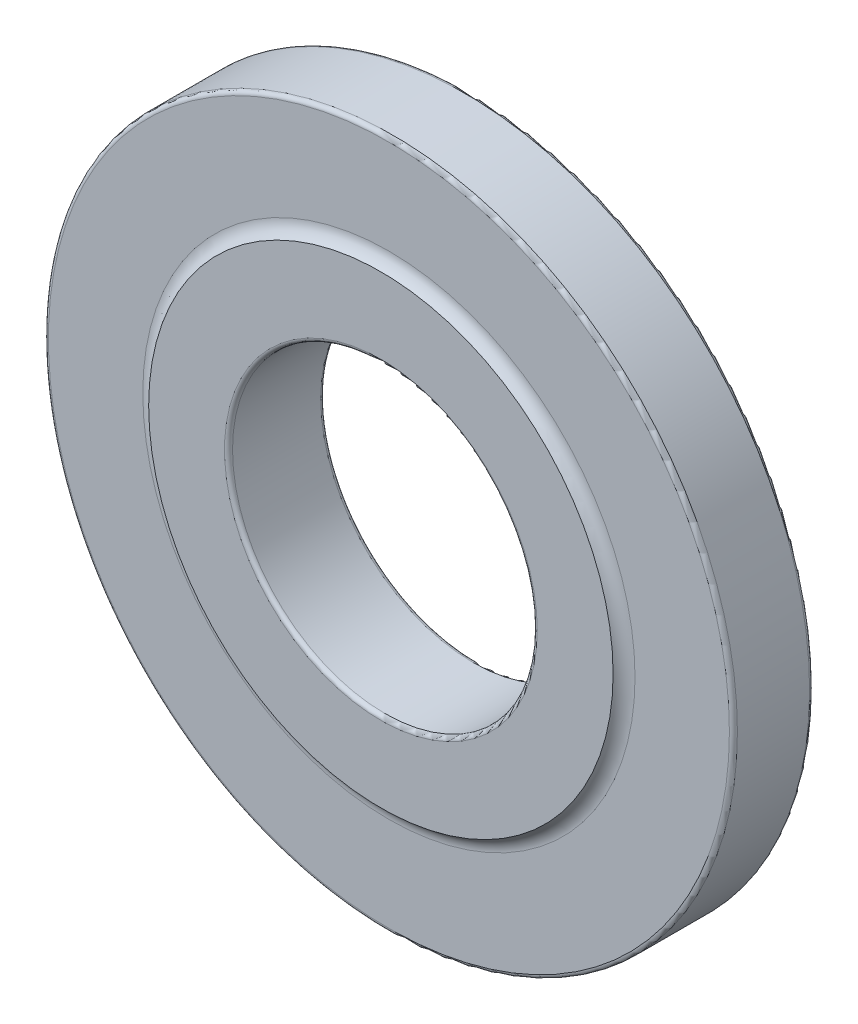
SolidWorks part; units mm, degrees
ref_plane "Plan de face" through (0, 0, 0) normal (0, 0, 1) x (1, 0, 0)
ref_plane "Plan de dessus" through (0, 0, 0) normal (0, 1, 0) x (1, 0, 0)
ref_plane "Plan de droite" through (0, 0, 0) normal (1, 0, 0) x (0, 0, -1)
sketch "Esquisse1" plane through (0, 0, 0) normal (0, 0, 1) x (1, 0, 0)
  line L0 (9.5, 0) -> (14.4778, 0) construction
  line L1 (14.4778, 0) -> (21.4762, 0) construction
  circle A0 centre (0, 0) radius 9.5
  circle A3 centre (0, 0) radius 14.4778
extrude "Boss.-Extru.1" add sketch "Esquisse1" along normal blind 3 and the other way blind 3
sketch "Esquisse3" plane through (0, 0, 0) normal (0, 0, 1) x (1, 0, 0)
  line L0 (14.4778, 0) -> (21.4781, 0) construction
  circle A0 centre (0, 0) radius 14.4778
  circle A1 centre (0, 0) radius 21.4781
extrude "Boss.-Extru.2" add sketch "Esquisse3" along normal blind 2.5 and the other way blind 2.5
fillet "Congé1" radius 0.25 2 edges at (21.4781, 0, -2.5) (21.4781, 0, 2.5)
fillet "Congé2" radius 1 2 edges at (14.4778, 0, -2.5) (14.4778, 0, 2.5)
fillet "Congé3" radius 0.25 2 edges at (9.5, 0, 3) (9.5, 0, -3)
